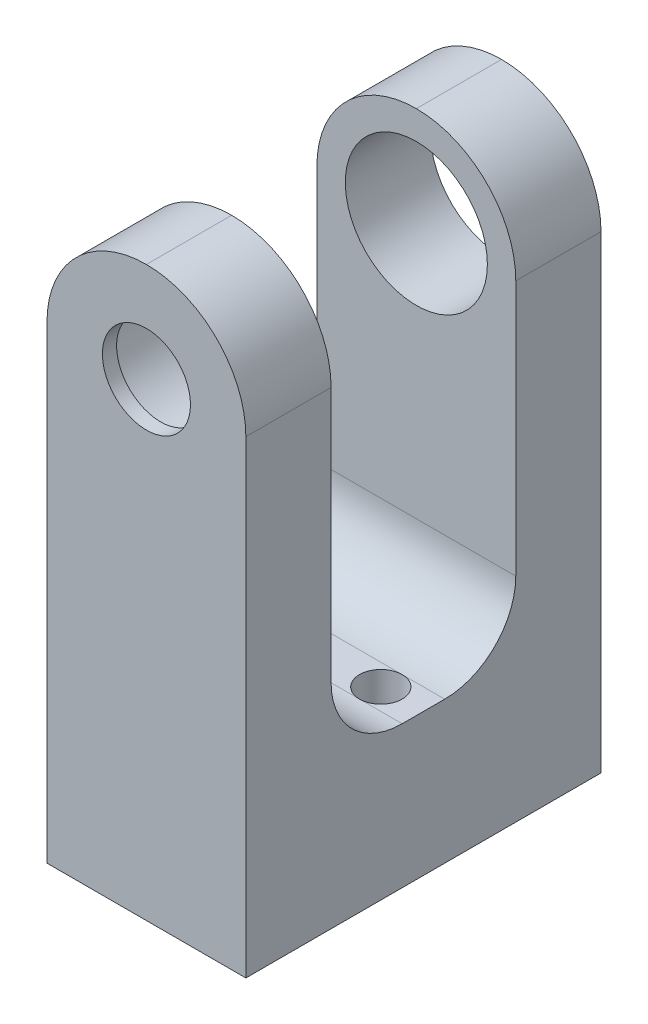
SolidWorks part; units mm, degrees
ref_plane "前视基准面" through (0, 0, 0) normal (0, 0, 1) x (1, 0, 0)
ref_plane "上视基准面" through (0, 0, 0) normal (0, 1, 0) x (1, 0, 0)
ref_plane "右视基准面" through (0, 0, 0) normal (1, 0, 0) x (0, 0, -1)
sketch "草图4" plane through (0, 0, 0) normal (1, 0, 0) x (0, 0, -1)
  line L0 (0, 0) -> (12.5, 0)
  line L1 (12.5, 0) -> (12.5, 40)
  line L2 (12.5, 40) -> (6.5, 40)
  line L3 (6.5, 40) -> (6.5, 15)
  line L4 (1.5, 10) -> (-1.5, 10)
  line L5 (-6.5, 15) -> (-6.5, 40)
  line L6 (-6.5, 40) -> (-12.5, 40)
  line L7 (-12.5, 40) -> (-12.5, 0)
  line L8 (-12.5, 0) -> (0, 0)
  arc A2 (6.5, 15) -> (1.5, 10) centre (1.5, 15) cw
  arc A3 (-1.5, 10) -> (-6.5, 15) centre (-1.5, 15) cw
  dimension "D5" = 5
  dimension "D1" = 40
  dimension "D2" = 12.5
  dimension "D3" = 6
  dimension "D4" = 10
extrude "凸台-拉伸1" add sketch "草图4" along normal blind 14
fillet "圆角1" radius 7 4 edges at (0, 40, 9.5) (0, 40, -9.5) (14, 40, -9.5) (14, 40, 9.5)
sketch "草图7" plane through (0, 0, 12.5) normal (0, 0, 1) x (1, 0, 0)
  circle A0 centre (7, 33) radius 5
extrude "切除-拉伸1" cut sketch "草图7" against normal blind 31 from offset 1 offset against normal yes
sketch "草图8" plane through (0, 0, 12.5) normal (0, 0, 1) x (1, 0, 0)
  circle A0 centre (7, 33) radius 3.1
extrude "切除-拉伸2" cut sketch "草图8" against normal blind 35 contours A0
sketch "草图10" plane through (0, 10, 0) normal (0, 1, 0) x (1, 0, 0)
  line L0 (0, 1.5) -> (0, -1.5) construction
  line L1 (14, 1.5) -> (14, -1.5) construction
  circle A0 centre (3, 0) radius 1.5
  circle A1 centre (11, 0) radius 1.5
  point P4 (0, 0)
  point P5 (0, 0)
  point P6 (0, 0)
  dimension "D1" = 3
  dimension "D2" = 3
extrude "切除-拉伸3" cut sketch "草图10" against normal blind 20
